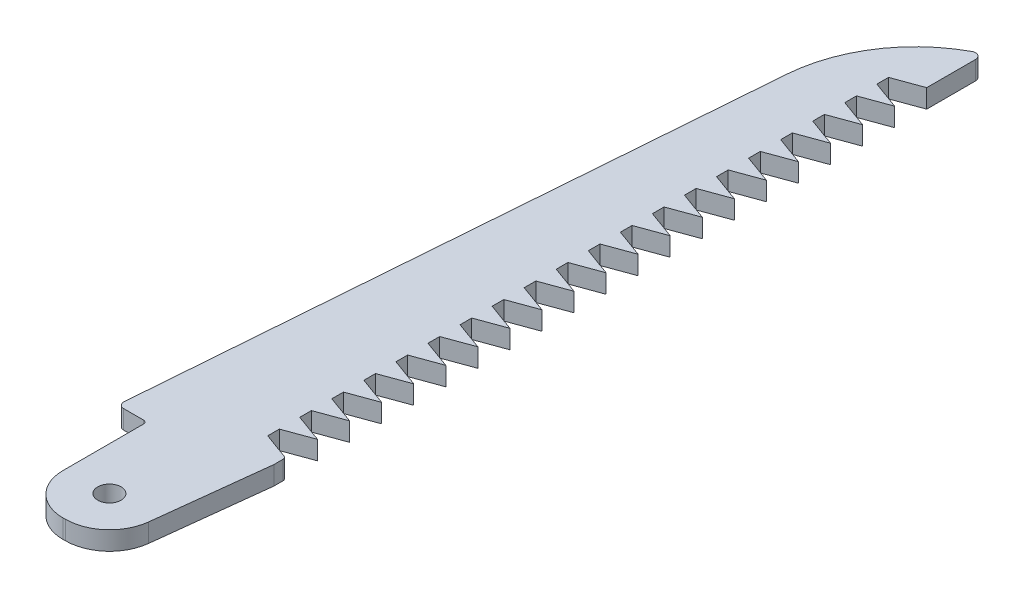
SolidWorks part; units mm, degrees
material "1060 Alloy"
ref_plane "Front Plane" through (0, 0, 0) normal (0, 0, 1) x (1, 0, 0)
ref_plane "Top Plane" through (0, 0, 0) normal (0, 1, 0) x (1, 0, 0)
ref_plane "Right Plane" through (0, 0, 0) normal (1, 0, 0) x (0, 0, -1)
sketch "Sketch2" plane through (0, 0, 0) normal (0, 1, 0) x (1, 0, 0)
  line L0 (0, 0) -> (0, 6)
  line L1 (0, 0) -> (11.5, 0) construction
  line L2 (0, 0) -> (0, 74) construction
  line L3 (0, 74) -> (11.5, 74) construction
  line L4 (11.5, 0) -> (11.5, 74) construction
  line L5 (0, 6) -> (4.5, 64)
  line L8 (10, 0) -> (0, 0)
  line L9 (11.5, 74) -> (11.5, 13)
  line L11 (10, 0) -> (11.5, 13)
  arc A0 (4.5, 64) -> (11.5, 74) centre (16.4695, 63.0713) cw
  circle A1 centre (6.6, 3.8) radius 1
  dimension "D6" = 10
  dimension "D8" = 2
  dimension "D1" = 11.5
  dimension "D2" = 74
  dimension "D3" = 10
  dimension "D4" = 6
  dimension "D5" = 7
  dimension "D7" = 61
  dimension "D9" = 3.8
  dimension "D10" = 6.6
extrude "Boss-Extrude1" add sketch "Sketch2" along normal blind 1.6
fillet "Fillet1" radius 3.8 1 edges at (10, 0.8, 0)
sketch "Sketch3" plane through (0, 1.6, 0) normal (0, 1, 0) x (1, 0, 0)
  line L1 (0, 0) -> (2.9, 0)
  line L2 (0, 0) -> (0, 10.72)
  line L3 (0, 10.72) -> (2.9, 10.72)
  line L4 (2.9, 0) -> (2.9, 10.72)
  dimension "D1" = 2.9
  dimension "D2" = 10.72
extrude "Cut-Extrude1" cut sketch "Sketch3" against normal through all
sketch "Sketch4" plane through (0, 1.6, 0) normal (0, 1, 0) x (1, 0, 0)
  line L0 (11.5, 69) -> (9.1, 68.125)
  line L1 (11.5, 13) -> (11.5, 74) construction
  line L2 (9.1, 68.125) -> (9.1, 67.125)
  line L3 (9.1, 67.125) -> (11.5, 66.25)
  line L4 (11.5, 66.25) -> (11.5, 69)
  dimension "D1" = 2.4
  dimension "D2" = 1
  dimension "D3" = 2.75
  dimension "D4" = 5
extrude "Cut-Extrude2" cut sketch "Sketch4" against normal through all
fillet "Fillet2" radius 0.5 1 edges at (11.5, 0.8, -74)
pattern_linear "LPattern1" count 20 spacing 2.75 along (0, 0, 1) of "Cut-Extrude2"
sketch "Sketch6" plane through (0, 0, 0) normal (0, -1, 0) x (1, 0, 0)
  line L0 (5.7455, -67.125) -> (4.9308, -56.625)
  line L1 (4.5, -64) -> (0.3662, -10.72) construction
  arc A0 (4.9308, -56.625) -> (5.7455, -67.125) centre (-2.4707, -62.4809) cw
  dimension "D1" = 1
  dimension "D2" = 10.5
extrude "Cut-Extrude5" cut sketch "Sketch6" against normal blind 0.5
fillet "Fillet3" radius 3 1 edges at (6.9389, 0.5, -61.7508)
fillet "Fillet4" radius 3.5 1 edges at (2.9, 0.8, 0)
fillet "Fillet5" radius 0.5 1 edges at (0.3662, 0.8, -10.72)
fillet "Fillet6" radius 0.3 2 edges at (11.5, 0.8, -14) (2.9, 0.8, -10.72)
